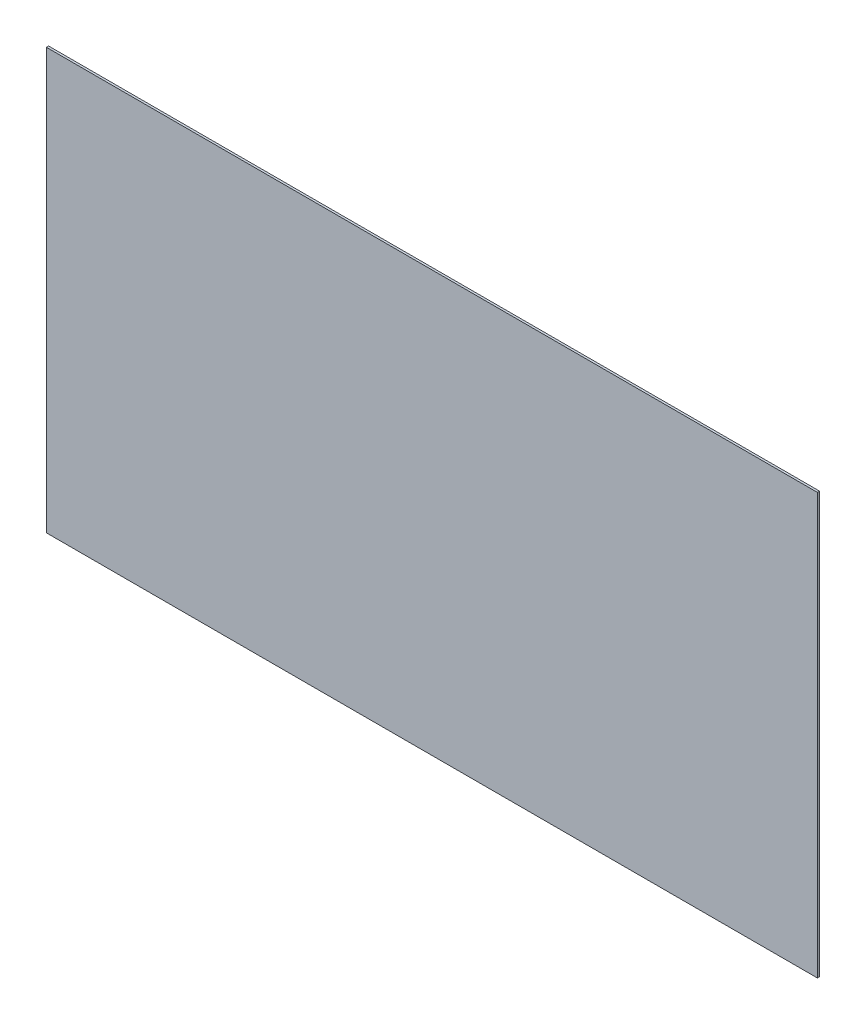
SolidWorks part; units mm, degrees
material "Acrylic (Medium-high impact)"
ref_plane "Front Plane" through (0, 0, 0) normal (0, 0, 1) x (1, 0, 0)
ref_plane "Top Plane" through (0, 0, 0) normal (0, 1, 0) x (1, 0, 0)
ref_plane "Right Plane" through (0, 0, 0) normal (1, 0, 0) x (0, 0, -1)
sketch "Sketch1" plane through (0, 0, 0) normal (0, 0, 1) x (1, 0, 0)
  line L1 (0, 0) -> (1117.6, 0)
  line L2 (0, 0) -> (0, 609.6)
  line L3 (0, 609.6) -> (1117.6, 609.6)
  line L4 (1117.6, 0) -> (1117.6, 609.6)
  dimension "D1" = 1117.6
  dimension "D2" = 609.6
extrude "Boss-Extrude1" add sketch "Sketch1" along normal blind 3.175
equation "\"W\"= 44in'width"
equation "\"L\"= 24in'length"
equation "\"t\"= 1 / 8in'thickness"
equation "\"D1@Sketch1\"=\"W\""
equation "\"D2@Sketch1\"=\"L\""
equation "\"D1@Boss-Extrude1\"=\"t\""
